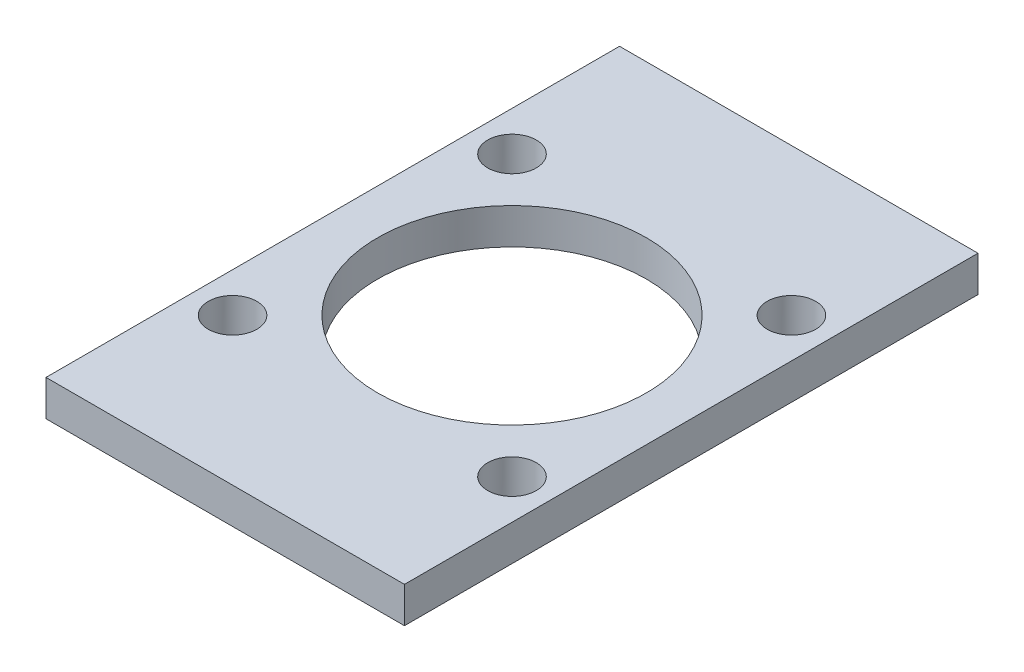
SolidWorks part; units mm, degrees
ref_plane "Front Plane" through (0, 0, 0) normal (0, 0, 1) x (1, 0, 0)
ref_plane "Top Plane" through (0, 0, 0) normal (0, 1, 0) x (1, 0, 0)
ref_plane "Right Plane" through (0, 0, 0) normal (1, 0, 0) x (0, 0, -1)
sketch "Sketch1" plane through (0, 0, 0) normal (0, 1, 0) x (1, 0, 0)
  line L1 (-15.875, -25.4) -> (15.875, -25.4)
  line L2 (-15.875, -25.4) -> (-15.875, 25.4)
  line L3 (-15.875, 25.4) -> (15.875, 25.4)
  line L4 (15.875, -25.4) -> (15.875, 25.4)
  line L5 (-15.875, -25.4) -> (15.875, 25.4) construction
  line L6 (-15.875, 25.4) -> (15.875, -25.4) construction
  point P0 (0, 0)
  dimension "D1" = 31.75
  dimension "D2" = 50.8
extrude "Boss-Extrude1" add sketch "Sketch1" along normal blind 3.175
sketch "Sketch2" plane through (0, 3.175, 0) normal (0, 1, 0) x (1, 0, 0)
  circle A0 centre (0, 0) radius 11.9062
  dimension "D1" = 23.8125
extrude "Cut-Extrude1" cut sketch "Sketch2" against normal up to next
hole_wizard "M4 Clearance Hole1" positions "Sketch4" profile "Sketch3" hole size "M4" standard "ANSI Metric" end condition up to next
sketch "Sketch4" plane through (0, 3.175, 0) normal (0, 1, 0) x (1, 0, 0)
  circle A0 centre (-12.3748, 12.3748) radius 2.15 construction
  circle A1 centre (12.3748, 12.3748) radius 2.15 construction
  circle A2 centre (-12.3748, -12.3748) radius 2.15 construction
  circle A3 centre (12.3748, -12.3748) radius 2.15 construction
  point P0 (12.3748, -12.3748)
  point P2 (-12.3748, -12.3748)
  point P4 (-12.3748, 12.3748)
  point P6 (12.3748, 12.3748)
sketch "Sketch3" plane through (12.3748, 3.175, 12.3748) normal (1, 0, 0) x (0, 0, 1)
  line L0 (0, 0) -> (0, 3.175)
  line L1 (0, 3.175) -> (2.15, 3.175)
  line L2 (2.15, 3.175) -> (2.15, 0)
  line L5 (2.15, 0) -> (0, 0)
  line L11 (0, -6.35) -> (0, 107.95) construction
  dimension "Thru Hole Dia." = 4.3
  dimension "Thru Hole Depth" = 3.175
